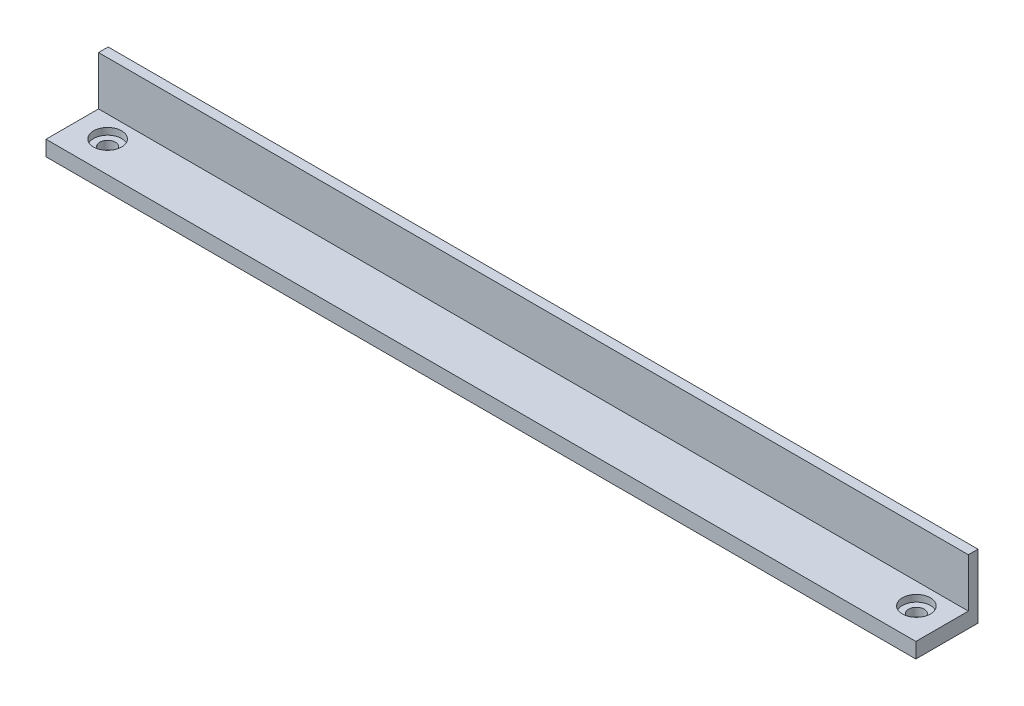
SolidWorks part; units mm, degrees
ref_plane "Front Plane" through (0, 0, 0) normal (0, 0, 1) x (1, 0, 0)
ref_plane "Top Plane" through (0, 0, 0) normal (0, 1, 0) x (1, 0, 0)
ref_plane "Right Plane" through (0, 0, 0) normal (1, 0, 0) x (0, 0, -1)
sketch "Sketch1" plane through (0, 0, 0) normal (0, 1, 0) x (1, 0, 0)
  line L0 (-142.5, 7.02) -> (142.5, 7.02)
  line L1 (-142.5, -10.18) -> (142.5, -10.18)
  line L2 (-142.5, -10.18) -> (-142.5, 10.18)
  line L3 (-142.5, 10.18) -> (142.5, 10.18)
  line L4 (142.5, -10.18) -> (142.5, 10.18)
  line L5 (-142.5, -10.18) -> (142.5, 10.18) construction
  line L6 (-142.5, 10.18) -> (142.5, -10.18) construction
  line L7 (0, 18.105) -> (0, -20.0728) construction
  circle A0 centre (132.5, 0) radius 2.55
  circle A1 centre (132.5, 0) radius 4.6
  circle A2 centre (-132.5, 0) radius 2.55
  circle A3 centre (-132.5, 0) radius 4.6
  point P0 (0, 0)
  dimension "D4" = 10
  dimension "D5" = 10.18
  dimension "D6" = 5.1
  dimension "D7" = 9.2
  dimension "D1" = 285
  dimension "D2" = 20.36
  dimension "D3" = 3.16
extrude "Boss-Extrude1" add sketch "Sketch1" along normal blind 5 contours L1 L4 L0 L2 A1 A3 | L0 L4 L3 L2 | A3 A2 | A1 A0 region at (0, 0, -8.6) region at (0, 0, 1.624) region at (128.0301, 0, 0) region at (-136.9699, 0, 0)
extrude "Boss-Extrude2" add sketch "Sketch1<3>" along normal blind 16 from surface contours L0 L4 L3 L2 region at (0, 0, -8.6) starting at face at (0, 5, 0)
sketch "Sketch1<3>" plane through (0, 0, 0) normal (0, 1, 0) x (1, 0, 0) same geometry as "Sketch1"
extrude "Cut-Extrude1" cut sketch "Sketch1<5>" against normal blind 2.2 from surface contours A3 A2 | A1 A0 region at (128.0301, 0, 0) region at (-136.9699, 0, 0) starting at face at (-132.5, 5, 2.55)
sketch "Sketch1<5>" plane through (0, 0, 0) normal (0, 1, 0) x (1, 0, 0) same geometry as "Sketch1"
